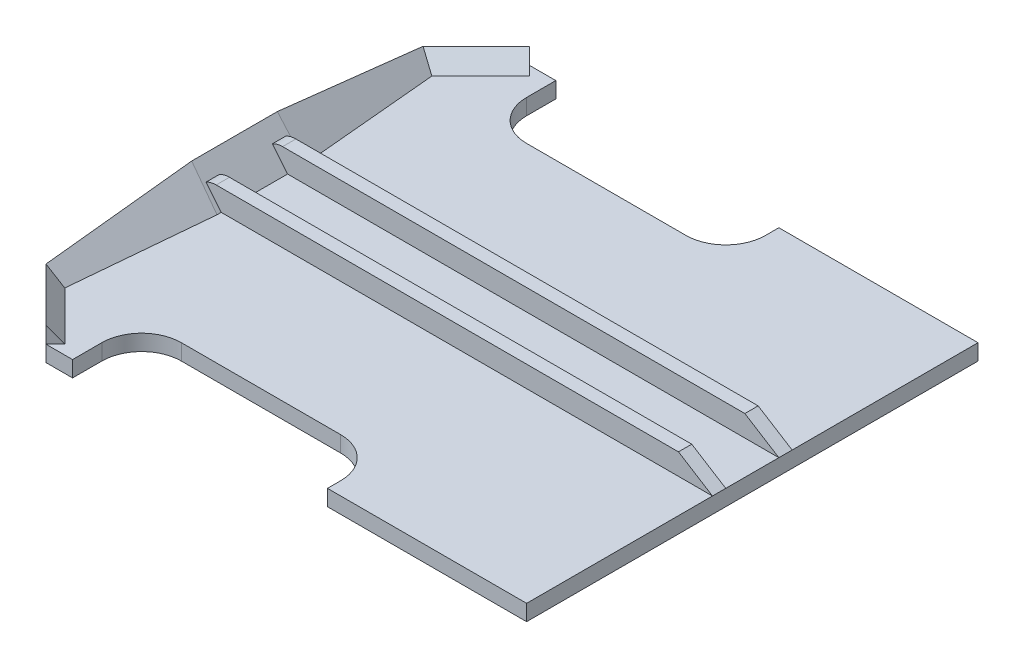
SolidWorks part; units mm, degrees
material "ABS"
ref_plane "Front Plane" through (0, 0, 0) normal (0, 0, 1) x (1, 0, 0)
ref_plane "Top Plane" through (0, 0, 0) normal (0, 1, 0) x (1, 0, 0)
ref_plane "Right Plane" through (0, 0, 0) normal (1, 0, 0) x (0, 0, -1)
sketch "Sketch1" plane through (0, 0, 0) normal (0, 1, 0) x (1, 0, 0)
  line L1 (-97.5, 85) -> (97.5, 85)
  line L2 (-97.5, 85) -> (-97.5, -85)
  line L3 (-97.5, -85) -> (97.5, -85)
  line L4 (97.5, 85) -> (97.5, -85)
  line L5 (-97.5, 85) -> (97.5, -85) construction
  line L6 (-97.5, -85) -> (97.5, 85) construction
  point P0 (0, 0)
  dimension "D1" = 195
  dimension "D2" = 170
extrude "Boss-Extrude1" add sketch "Sketch1" along normal blind 6
sketch "Sketch2" plane through (0, 6, 0) normal (0, 1, 0) x (1, 0, 0)
  line L0 (-97.5, -85) -> (-67.5, -85) construction
  line L1 (-97.5, -85) -> (97.5, -85) construction
  line L2 (0, 0) -> (-97.5, 0) construction
  line L3 (-67.5, -85) -> (22.5, -85)
  line L4 (-67.5, -85) -> (-67.5, -65)
  line L5 (-67.5, -65) -> (22.5, -65)
  line L6 (22.5, -85) -> (22.5, -65)
  line L7 (-97.5, 85) -> (-97.5, -85) construction
  line L8 (-67.5, 65) -> (22.5, 65)
  line L9 (22.5, 85) -> (22.5, 65)
  line L10 (-67.5, 85) -> (22.5, 85)
  line L11 (-67.5, 85) -> (-67.5, 65)
  dimension "D1" = 30
  dimension "D2" = 90
  dimension "D3" = 20
extrude "Cut-Extrude1" cut sketch "Sketch2" against normal through all
fillet "Fillet1" radius 15 4 edges at (22.5, 3, -65) (-67.5, 3, -65) (-67.5, 3, 65) (22.5, 3, 65)
sketch "Sketch3" plane through (0, 6, 0) normal (0, 1, 0) x (1, 0, 0)
  line L0 (0, 0) -> (-97.5, 0) construction
  line L1 (-67.5, 85) -> (-97.5, 85)
  line L2 (-67.5, 85) -> (-67.5, 91)
  line L3 (-67.5, 91) -> (-97.5, 91)
  line L4 (-97.5, 85) -> (-97.5, 91)
  line L5 (-97.5, 85) -> (-97.5, -85) construction
  line L6 (-67.5, -91) -> (-97.5, -91)
  line L7 (-97.5, -85) -> (-97.5, -91)
  line L8 (-67.5, -85) -> (-97.5, -85)
  line L9 (-67.5, -85) -> (-67.5, -91)
  dimension "D1" = 6
extrude "Boss-Extrude2" add sketch "Sketch3" against normal up to surface (6 mm away) up to face at (-16.875, 0, 0)
chamfer "Chamfer1" distance 20 angle 45 2 edges at (-97.5, 3, -91) (-97.5, 3, 91)
sketch "Sketch4" plane through (0, 0, 0) normal (0, -1, 0) x (1, 0, 0)
  line L0 (51.5, -75) -> (82.1667, -75) construction
  line L1 (143.5, -85) -> (51.5, -85) construction
  line L2 (143.5, -85) -> (143.5, -65) construction
  line L3 (143.5, -65) -> (51.5, -65) construction
  line L4 (51.5, -85) -> (51.5, -65) construction
  line L5 (82.1667, -75) -> (112.8333, -75) construction
  line L6 (-77.5, -91) -> (-67.5, -91) construction
  line L7 (-67.5, -91) -> (-67.5, -80) construction
  line L9 (97.5, -85) -> (22.5, -85) construction
  line L10 (112.8333, -75) -> (143.5, -75) construction
  line L11 (97.5, 85) -> (97.5, -85) construction
  line L12 (0, 0) -> (97.5, 0) construction
  circle A0 centre (82.1667, -75) radius 6.1
  circle A1 centre (82.1667, 75) radius 6.1
  circle A2 centre (-75.5, -79.6) radius 6.1
  circle A3 centre (-75.5, 79.6) radius 6.1
  point P7 (97.5, -75)
  dimension "D3" = 12.2
  dimension "D6" = 12.2
  dimension "D1" = 92
  dimension "D2" = 20
  dimension "D4" = 11.4
  dimension "D5" = 8
extrude "Cut-Extrude2" cut sketch "Sketch4" against normal blind 3.2
fillet "Fillet2" radius 0.2 4 edges at (82.1667, 0, 81.1) (82.1667, 0, -81.1) (-75.5, 0, 85.7) (-75.5, 0, -85.7)
sketch "Sketch5" plane through (0, 6, 0) normal (0, 1, 0) x (1, 0, 0)
  line L0 (97.5, -85) -> (97.5, 85) construction
  line L1 (97.5, -10) -> (-97.4, -10)
  line L2 (97.5, -10) -> (97.5, -15)
  line L3 (97.5, -15) -> (-97.4, -15)
  line L4 (-97.4, -10) -> (-97.4, -15)
  line L6 (-97.5, 71) -> (-97.5, -71) construction
  line L7 (22.5, -85) -> (97.5, -85) construction
  line L8 (-97.4, 10) -> (97.5, 10)
  line L9 (-97.4, 10) -> (-97.4, 15)
  line L10 (-97.4, 15) -> (97.5, 15)
  line L11 (97.5, 10) -> (97.5, 15)
  line L12 (97.5, 85) -> (22.5, 85) construction
  dimension "D1" = 70
  dimension "D2" = 70
  dimension "D3" = 5
  dimension "D4" = 5
  dimension "D5" = 0.1
extrude "Boss-Extrude3" add sketch "Sketch5" along normal blind 8
chamfer "Chamfer2" distance 8 angle 58 2 edges at (97.5, 14, 12.5) (97.5, 14, -12.5) first distance on face at (97.5, 7.6667, 0)
fillet "Fillet3" radius 8 2 edges at (-97.4, 14, 12.5) (-97.4, 14, -12.5)
sketch "Sketch6" plane through (0, 6, 0) normal (0, 1, 0) x (1, 0, 0)
  line L0 (-97.5, -71) -> (-77.5, -91) construction
  line L2 (-77.5, 91) -> (-97.5, 71) construction
  line L3 (-97.5, -71) -> (-77.5, -91)
  line L5 (-77.5, 91) -> (-97.5, 71)
  line L14 (-73.9645, 87.4645) -> (-92.3079, 69.1211)
  line L15 (-92.3079, 69.1211) -> (-87.5161, 16.5851)
  line L16 (-87.5161, 10) -> (-87.5161, 16.5851)
  line L17 (-87.5161, 10) -> (-87.5161, -10)
  line L18 (-87.5161, -16.5851) -> (-87.5161, -10)
  line L19 (-87.5161, -16.5851) -> (-92.3079, -69.1211)
  line L20 (-92.3079, -69.1211) -> (-73.9645, -87.4645)
  line L21 (-77.5, -91) -> (-73.9645, -87.4645)
  line L22 (-77.5, 91) -> (-73.9645, 87.4645)
  line L23 (-97.5, 71) -> (-92.5161, 16.3575) construction
  line L24 (-92.5161, 10) -> (-92.5161, 16.3575) construction
  line L25 (-92.5161, 10) -> (-92.5161, -10) construction
  line L26 (-92.5161, -16.3575) -> (-92.5161, -10) construction
  line L27 (-92.5161, -16.3575) -> (-97.5, -71) construction
  line L28 (-97.5, 71) -> (-97.5, -71)
  line L30 (-89.4, 10) -> (84.6973, 10) construction
  line L32 (84.6973, -10) -> (-89.4, -10) construction
  dimension "D2" = 52.754
  dimension "D3" = 52.754
  dimension "D1" = 5
extrude "Boss-Extrude4" add sketch "Sketch6" along normal blind 15 separate body
chamfer "Chamfer3" distance 15 angle 39 5 edges at (-83.1362, 21, -78.2928) (-87.5161, 21, 0) (-83.1362, 21, 78.2928) (-89.912, 21, -42.8531) (-89.912, 21, 42.8531) first distance on face at (-83.1362, 13.5, -78.2928) first distance on face at (-87.5161, 13.5, 0) first distance on face at (-83.1362, 13.5, 78.2928) first distance on face at (-89.912, 13.5, -42.8531) first distance on face at (-89.912, 13.5, 42.8531)
